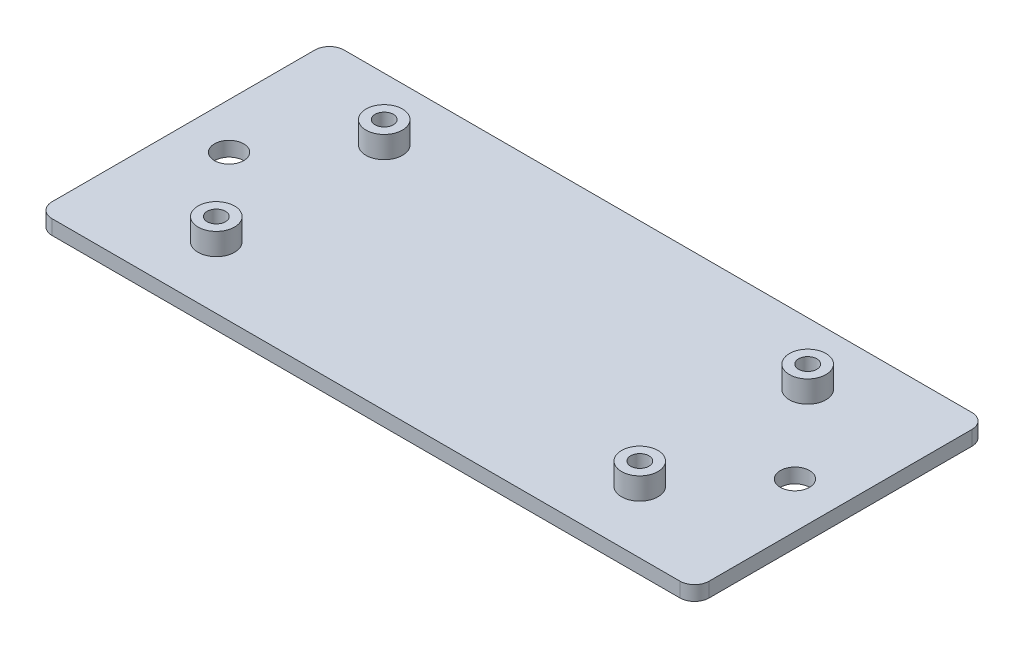
SolidWorks part; units mm, degrees
ref_plane "Спереди" through (0, 0, 0) normal (0, 0, 1) x (1, 0, 0)
ref_plane "Сверху" through (0, 0, 0) normal (0, 1, 0) x (1, 0, 0)
ref_plane "Справа" through (0, 0, 0) normal (1, 0, 0) x (0, 0, -1)
sketch "Эскиз1" plane through (0, 0, 0) normal (0, 1, 0) x (1, 0, 0)
  line L1 (0, 0) -> (90, 0)
  line L2 (0, 0) -> (0, -40)
  line L3 (0, -40) -> (90, -40)
  line L4 (90, 0) -> (90, -40)
  dimension "D1" = 90
  dimension "D2" = 40
extrude "Бобышка-Вытянуть1" add sketch "Эскиз1" along normal blind 2
sketch "Эскиз2" plane through (0, 2, 0) normal (0, 1, 0) x (1, 0, 0)
  line L0 (0, 0) -> (0, -40) construction
  line L1 (90, -40) -> (90, 0) construction
  line L2 (90, 0) -> (0, 0) construction
  line L3 (0, -40) -> (90, -40) construction
  circle A0 centre (16, -8.5) radius 2.5
  circle A1 centre (16, -31.5) radius 2.5
  circle A2 centre (74, -8.5) radius 2.5
  circle A3 centre (74, -31.5) radius 2.5
  dimension "D1" = 16
  dimension "D2" = 16
  dimension "D3" = 16
  dimension "D4" = 16
  dimension "D5" = 8.5
  dimension "D6" = 8.5
  dimension "D7" = 5
  dimension "D8" = 8.5
  dimension "D9" = 8.5
  dimension "D10" = 5
  dimension "D11" = 5
  dimension "D12" = 5
extrude "Бобышка-Вытянуть2" add sketch "Эскиз2" along normal blind 3
sketch "Эскиз3" plane through (0, 5, 0) normal (0, 1, 0) x (1, 0, 0)
  circle A0 centre (16, -8.5) radius 1.25
  circle A1 centre (16, -31.5) radius 1.25
  circle A2 centre (74, -8.5) radius 1.25
  circle A3 centre (74, -31.5) radius 1.25
  dimension "D1" = 2.5
  dimension "D2" = 2.5
  dimension "D3" = 2.5
  dimension "D4" = 2.5
extrude "Вырез-Вытянуть1" cut sketch "Эскиз3" against normal through all both and the other way through all
sketch "Эскиз4" plane through (0, 2, 0) normal (0, 1, 0) x (1, 0, 0)
  line L0 (0, -20) -> (90, -20) construction
  line L1 (0, 0) -> (0, -40) construction
  line L2 (90, -40) -> (90, 0) construction
  circle A0 centre (6.25, -20) radius 2
  circle A1 centre (83.75, -20) radius 2
  dimension "D2" = 6.25
  dimension "D3" = 4
  dimension "D4" = 4
  dimension "D1" = 6.25
extrude "Вырез-Вытянуть2" cut sketch "Эскиз4" against normal through all
fillet "Скругление1" radius 2 1 edges at (0, 1, 0) type face fillet first side face at (0, 1, 20) second side face at (45, 1, 0)
fillet "Скругление2" radius 2 1 edges at (0, 1, 40) type face fillet first side face at (0, 1, 21) second side face at (45, 1, 40)
fillet "Скругление3" radius 2 1 edges at (90, 1, 40) type face fillet first side face at (46, 1, 40) second side face at (90, 1, 20)
fillet "Скругление4" radius 2 1 edges at (90, 1, 0) type face fillet first side face at (46, 1, 0) second side face at (90, 1, 19)
